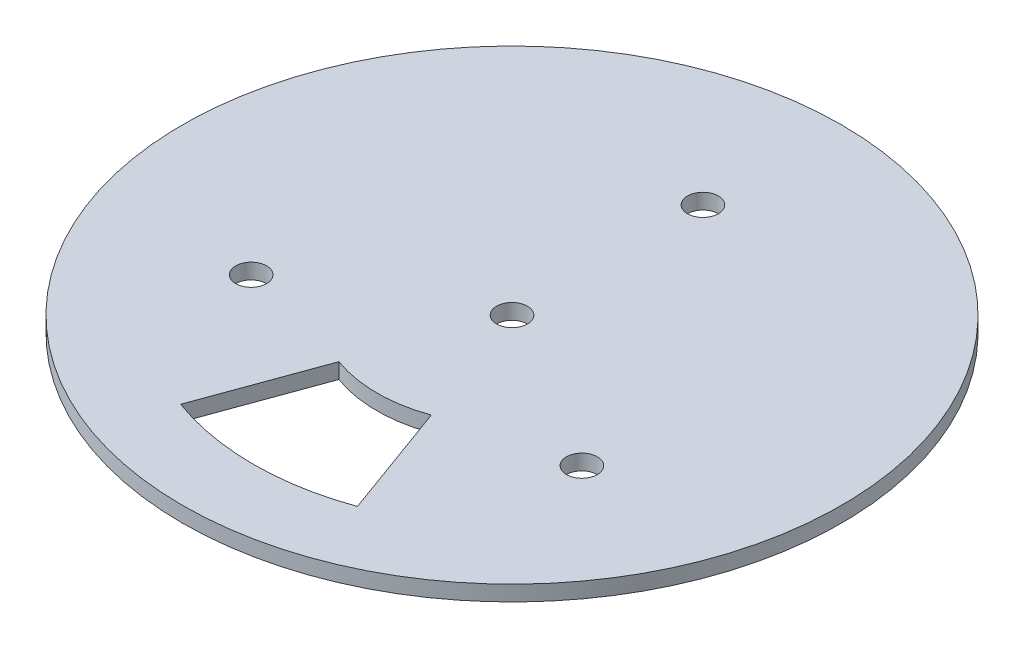
SolidWorks part; units mm, degrees
ref_plane "Plano frontal" through (0, 0, 0) normal (0, 0, 1) x (1, 0, 0)
ref_plane "Plano superior" through (0, 0, 0) normal (0, 1, 0) x (1, 0, 0)
ref_plane "Plano direito" through (0, 0, 0) normal (1, 0, 0) x (0, 0, -1)
sketch "Esboço1" plane through (0, 0, 0) normal (0, 1, 0) x (1, 0, 0)
  circle A0 centre (0, 0) radius 85.4
  dimension "D1" = 170.8
extrude "Ressalto-extrusão1" add sketch "Esboço1" along normal blind 4
sketch "Esboço3" plane through (0, 0, 0) normal (0, -1, 0) x (1, 0, 0)
  line L0 (11.9707, 32.8892) -> (22.9153, 62.9594)
  line L1 (-11.9707, 32.8892) -> (-22.9153, 62.9594)
  line L3 (0, 91.1664) -> (0, -117.3815) construction
  circle A1 centre (0, 0) radius 87.65
  circle A2 centre (0, 0) radius 87.65
  arc A3 (11.9707, 32.8892) -> (-11.9707, 32.8892) centre (0, 0) ccw
  arc A4 (22.9153, 62.9594) -> (-22.9153, 62.9594) centre (0, 0) ccw
  dimension "D2" = 70
  dimension "D3" = 134
  dimension "D4" = 20
  dimension "D5" = 20
  dimension "D1" = 0
extrude "Corte-extrusão2" cut sketch "Esboço3" against normal through all contours L0 A4 L1 A3
sketch "Esboço4" plane through (0, 4, 0) normal (0, 1, 0) x (1, 0, 0)
  circle A0 centre (42.8509, -24.74) radius 4
  circle A1 centre (0, 49.48) radius 4
  circle A2 centre (-42.8509, -24.74) radius 4
  point P0 (0, 49.48)
  point P2 (-42.8509, -24.74)
  point P4 (42.8509, -24.74)
extrude "Corte-extrusão3" cut sketch "Esboço4" against normal through all
sketch "Esboço5" plane through (0, 0, 0) normal (0, -1, 0) x (1, 0, 0)
  circle A1 centre (0, 0) radius 4
extrude "Corte-extrusão4" cut sketch "Esboço5" against normal through all
